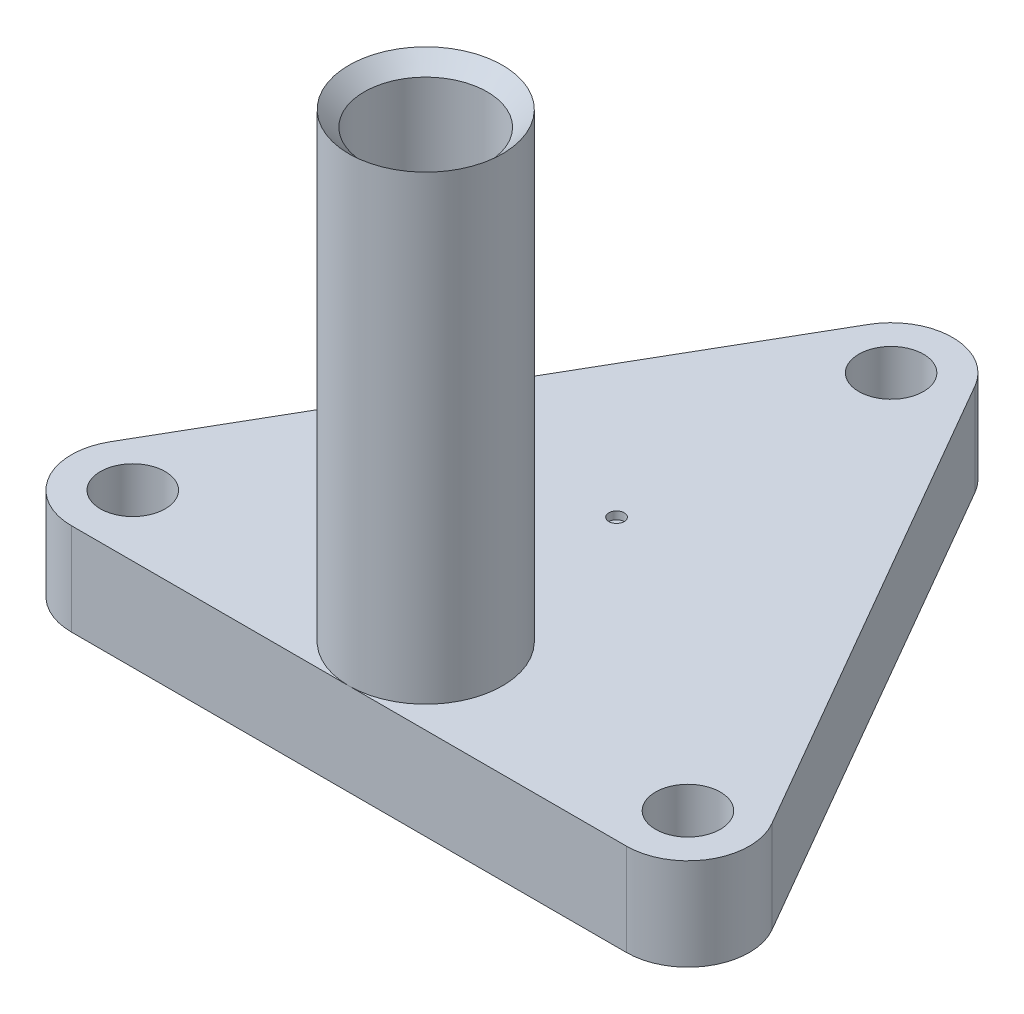
SolidWorks part; units mm, degrees
ref_plane "Front Plane" through (0, 0, 0) normal (0, 0, 1) x (1, 0, 0)
ref_plane "Top Plane" through (0, 0, 0) normal (0, 1, 0) x (1, 0, 0)
ref_plane "Right Plane" through (0, 0, 0) normal (1, 0, 0) x (0, 0, -1)
sketch "Sketch1" plane through (0, 0, 0) normal (0, 1, 0) x (1, 0, 0)
  line L0 (0, 0) -> (9.0359, 0)
  line L1 (10.7679, 3) -> (1.7321, 18.6506)
  line L2 (-1.7321, 18.6506) -> (-10.7679, 3)
  line L3 (-9.0359, 0) -> (0, 0)
  arc A0 (9.0359, 0) -> (10.7679, 3) centre (9.0359, 2) ccw
  arc A1 (-10.7679, 3) -> (-9.0359, 0) centre (-9.0359, 2) ccw
  arc A2 (1.7321, 18.6506) -> (-1.7321, 18.6506) centre (0, 17.6506) ccw
  circle A3 centre (0, 17.6506) radius 1.054
  circle A4 centre (-9.0359, 2) radius 1.054
  circle A5 centre (9.0359, 2) radius 1.054
  point P7 (12.5, 0)
  point P10 (-12.5, 0)
  point P13 (0, 21.6506)
  dimension "D5" = 2
  dimension "D1" = 60
  dimension "D2" = 60
  dimension "D3" = 25
  dimension "D4" = 12.5
extrude "Boss-Extrude1" add sketch "Sketch1" along normal blind 3
sketch "Sketch2" plane through (0, 3, 0) normal (0, 1, 0) x (1, 0, 0)
  circle A0 centre (0, 2.5) radius 0.8
  dimension "D1" = 2.5
extrude "Cut-Extrude1" cut sketch "Sketch2" against normal through all
sketch "Sketch3" plane through (0, 3, 0) normal (0, 1, 0) x (1, 0, 0)
  circle A1 centre (0, 2.5) radius 2.5
extrude "Boss-Extrude2" add sketch "Sketch3" along normal blind 15
sketch "Sketch4" plane through (0, 3, 0) normal (0, 1, 0) x (1, 0, 0)
  circle A0 centre (0, 2.5) radius 2
extrude "Cut-Extrude2" cut sketch "Sketch4" along normal up to next
chamfer "Chamfer1" distance 2 angle 20 1 edges at (0, 3, -0.5) first distance on face at (0, 18, -0.5)
chamfer "Chamfer2" distance 0.5 angle 45 1 edges at (0, 18, -0.5)
sketch "Sketch5" plane through (0, 3, 0) normal (0, 1, 0) x (1, 0, 0)
  line L0 (-9.0359, 0) -> (0, 0) construction
  circle A0 centre (-0.4007, 9.1131) radius 0.25
  point P2 (-4.5179, 0)
  dimension "D1" = 10
extrude "Cut-Extrude3" cut sketch "Sketch5" against normal blind 0.25
